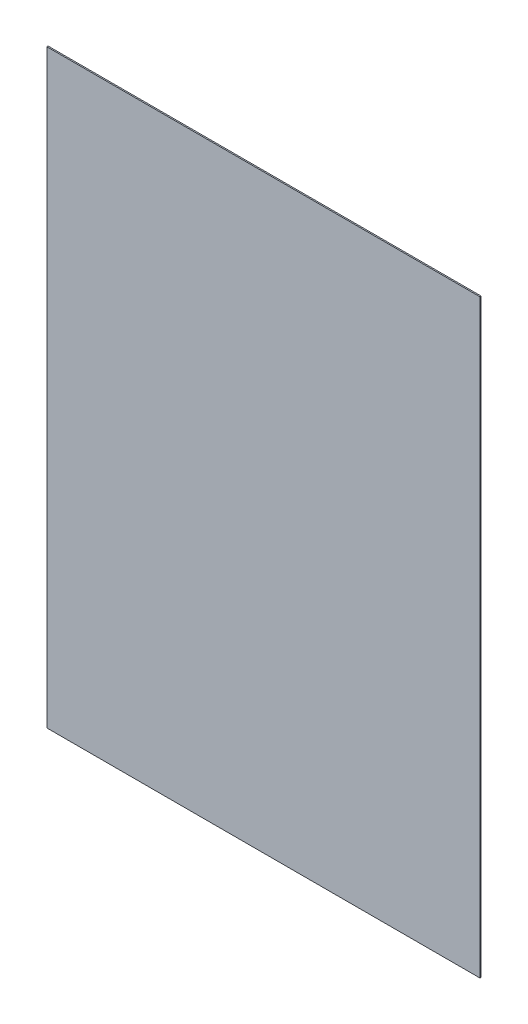
SolidWorks part; units mm, degrees
material "Akryl (Średnie-wysokie uderzenie)"
ref_plane "Płaszczyzna przednia" through (0, 0, 0) normal (0, 0, 1) x (1, 0, 0)
ref_plane "Płaszczyzna górna" through (0, 0, 0) normal (0, 1, 0) x (1, 0, 0)
ref_plane "Płaszczyzna prawa" through (0, 0, 0) normal (1, 0, 0) x (0, 0, -1)
sketch "Szkic1" plane through (0, 0, 0) normal (0, 0, 1) x (1, 0, 0)
  line L1 (0, 0) -> (1380, 0)
  line L2 (0, 0) -> (0, 1880)
  line L3 (0, 1880) -> (1380, 1880)
  line L4 (1380, 0) -> (1380, 1880)
  dimension "D1" = 1380
  dimension "D2" = 1880
base flange "Odgięcie bazowe1" sketch "Szkic1" thickness 4 reverse thickness direction no parameters "D1"=4
sketch "Linie zgięcia1" [suppressed] plane through (0, 0, 0) normal (0, 1, 0) x (1, 0, 0)
sketch "Ramka-graniczna1" [suppressed] plane through (0, 0, 0) normal (0, 1, 0) x (1, 0, 0)
sheet metal parameters "Arkusz blachy1" thickness 4 parameters "D1"=4
flat pattern "Rozłożony model1" [suppressed]
sketch "Linie zgięcia2" plane through (0, 0, 0) normal (0, 1, 0) x (1, 0, 0)
sketch3d "Ramka-graniczna2" [suppressed]
  line L0 (-1380, 1880, 0) -> (-1380, 0, 0) construction
  line L1 (0, 1880, 0) -> (0, 0, 0) construction
  line L2 (-1380, 1880, 0) -> (0, 1880, 0) construction
  line L3 (-1380, 0, 0) -> (0, 0, 0) construction
